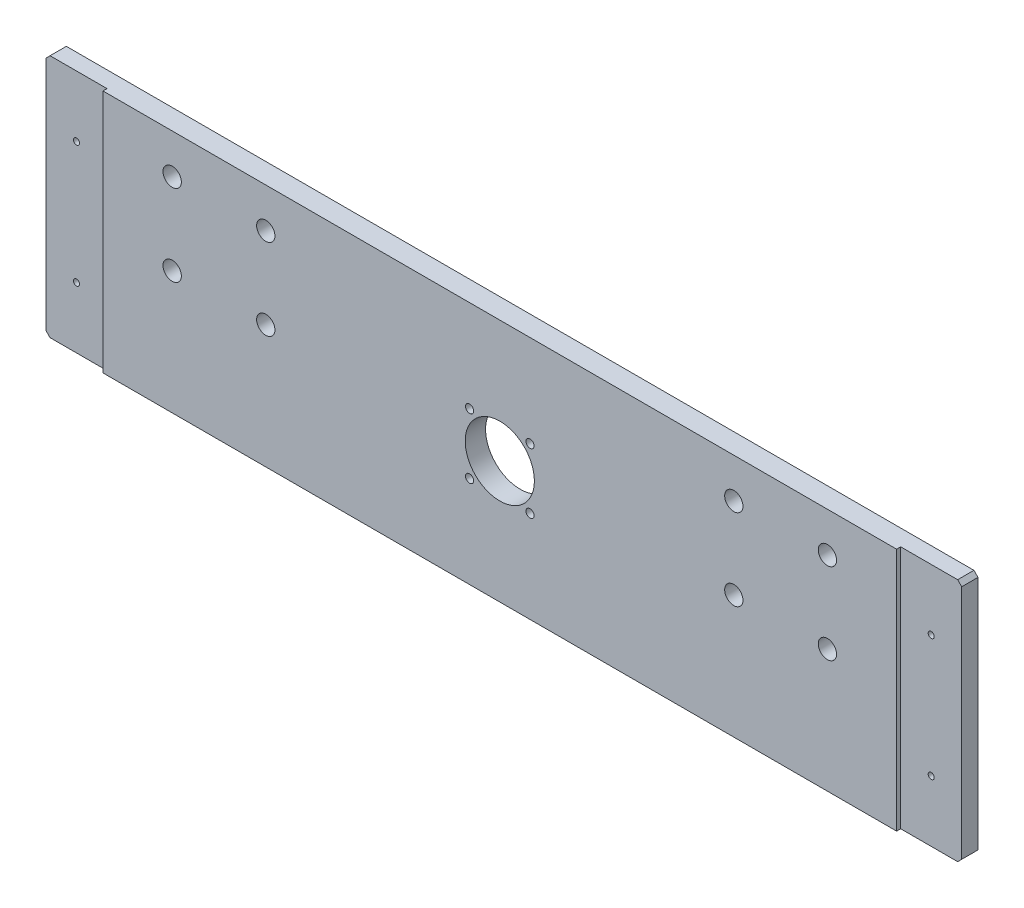
SolidWorks part; units mm, degrees
ref_plane "Piano frontale" through (0, 0, 0) normal (0, 0, 1) x (1, 0, 0)
ref_plane "Piano superiore" through (0, 0, 0) normal (0, 1, 0) x (1, 0, 0)
ref_plane "Piano destro" through (0, 0, 0) normal (1, 0, 0) x (0, 0, -1)
sketch "Schizzo1" plane through (0, 0, 0) normal (0, 0, 1) x (1, 0, 0)
  line L0 (225, 120) -> (225, 0) construction
  line L1 (2, 0) -> (448, 0)
  line L2 (0, 2) -> (0, 118)
  line L3 (2, 120) -> (448, 120)
  line L4 (450, 2) -> (450, 118)
  line L5 (225, 60) -> (199.8765, 85.1235) construction
  line L7 (225, 60) -> (243.5099, 60) construction
  line L21 (0, 118) -> (2, 120)
  line L22 (2, 0) -> (0, 2)
  line L23 (448, 0) -> (450, 2)
  line L24 (448, 120) -> (450, 118)
  line L25 (225, 60) -> (450, 60) construction
  circle A0 centre (225, 60) radius 17
  circle A1 centre (225, 60) radius 21 construction
  circle A2 centre (239.8492, 74.8492) radius 2
  circle A3 centre (386, 100.5) radius 4.5
  circle A4 centre (239.8492, 45.1508) radius 2
  circle A5 centre (210.1508, 45.1508) radius 2
  circle A6 centre (110, 100.5) radius 4.5
  circle A7 centre (110, 60.5) radius 4.5
  circle A8 centre (64, 60.5) radius 4.5
  circle A9 centre (64, 100.5) radius 4.5
  circle A10 centre (386, 60.5) radius 4.5
  circle A11 centre (15, 30) radius 1.5
  circle A12 centre (435, 30) radius 1.5
  circle A13 centre (210.1508, 74.8492) radius 2
  circle A14 centre (340, 60.5) radius 4.5
  circle A15 centre (340, 100.5) radius 4.5
  circle A17 centre (435, 90) radius 1.5
  circle A18 centre (15, 90) radius 1.5
  point P0 (0, 0)
  point P1 (450, 120)
  point P2 (0, 120)
  point P3 (450, 0)
  point P13 (210.1508, 74.8492)
  point P14 (239.8492, 74.8492)
  point P15 (210.1508, 45.1508)
  point P17 (239.8492, 45.1508)
  dimension "D4" = 34
  dimension "D15" = 3
  dimension "D17" = 4
  dimension "D8" = 42
  dimension "D1" = 120
  dimension "D2" = 450
  dimension "D3" = 60
  dimension "D5" = 45
  dimension "D14" = 30
  dimension "D16" = 15
extrude "Estrusione-Estrusione1" add sketch "Schizzo1" against normal blind 10
sketch "Schizzo2" plane through (0, 0, 0) normal (0, 0, 1) x (1, 0, 0)
  line L0 (448, 120) -> (2, 120) construction
  line L1 (30, 120) -> (0, 120)
  line L2 (30, 120) -> (30, 0)
  line L3 (30, 0) -> (0, 0)
  line L4 (0, 120) -> (0, 0)
  line L5 (225, 120) -> (225, -23.5993) construction
  line L6 (450, 120) -> (450, 0)
  line L7 (420, 0) -> (450, 0)
  line L8 (420, 120) -> (420, 0)
  line L9 (420, 120) -> (450, 120)
  dimension "D1" = 30
extrude "Taglio-Estrusione1" cut sketch "Schizzo2" against normal blind 2
